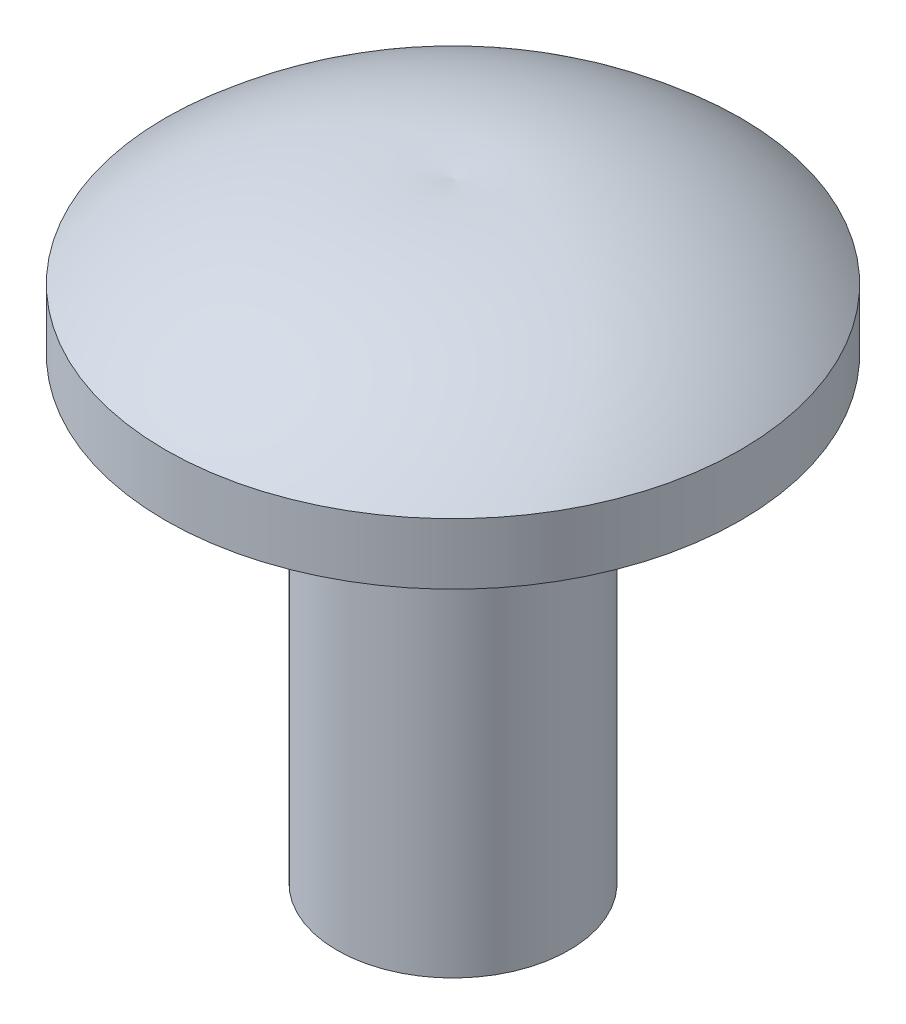
SolidWorks part; units mm, degrees
ref_plane "Front Plane" through (0, 0, 0) normal (0, 0, 1) x (1, 0, 0)
ref_plane "Top Plane" through (0, 0, 0) normal (0, 1, 0) x (1, 0, 0)
ref_plane "Right Plane" through (0, 0, 0) normal (1, 0, 0) x (0, 0, -1)
sketch "Sketch1" plane through (0, 0, 0) normal (0, 0, 1) x (1, 0, 0)
  line L0 (0, 0) -> (0, 12.7) construction
  line L1 (0, 0) -> (2.413, 0)
  line L2 (2.413, 0) -> (2.413, 9.525)
  line L3 (2.413, 9.525) -> (5.9802, 9.525)
  line L4 (5.9802, 9.525) -> (5.9802, 10.795)
  line L7 (0, 0) -> (0, 12.7)
  arc A0 (0, 12.7) -> (5.9802, 10.795) centre (0.8487, 5.0252) cw
  dimension "D3" = 7.7216
  dimension "D1" = 12.7
  dimension "D2" = 4.826
  dimension "D4" = 9.525
  dimension "D5" = 1.27
  dimension "D6" = 0.8487
revolve "Revolve1" add sketch "Sketch1" angle 360 about L7
sketch "Sketch2" plane through (0, 0, 0) normal (0, 0, 1) x (1, 0, 0)
  line L0 (0.8487, 12.7468) -> (0.8487, 11.9991)
  line L1 (0.8487, 11.9991) -> (4.1634, 11.9991)
  arc A0 (5.9802, 10.795) -> (0.8487, 12.7468) centre (0.8487, 5.0252) ccw construction
  arc A1 (4.1634, 11.9991) -> (0.8487, 12.7468) centre (0.8487, 5.0252) ccw
  dimension "D1" = 4.1634
